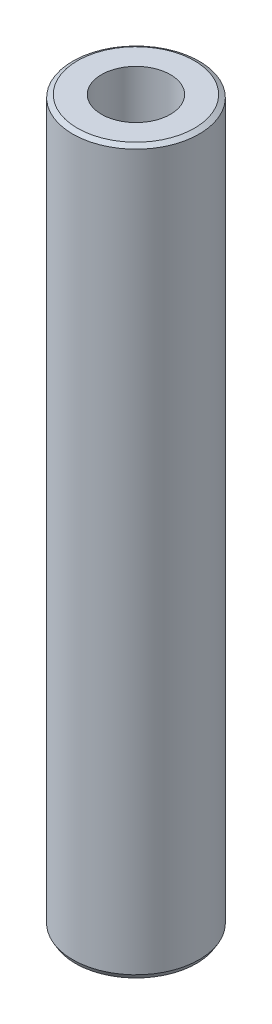
SolidWorks part; units mm, degrees
ref_plane "Front Plane" through (0, 0, 0) normal (0, 0, 1) x (1, 0, 0)
ref_plane "Top Plane" through (0, 0, 0) normal (0, 1, 0) x (1, 0, 0)
ref_plane "Right Plane" through (0, 0, 0) normal (1, 0, 0) x (0, 0, -1)
sketch "Sketch1" plane through (0, 0, 0) normal (0, 1, 0) x (1, 0, 0)
  circle A0 centre (0, 0) radius 52.5
  dimension "SHAFT_OD" = 105
extrude "Boss-Extrude1" add sketch "Sketch1" along normal blind 600
sketch "Sketch2" plane through (0, 0, 0) normal (0, 1, 0) x (1, 0, 0)
  circle A0 centre (0, 0) radius 28.6177
  dimension "BORE_D" = 57.2355
extrude "Cut-Extrude1" cut sketch "Sketch2" along normal through all
chamfer "Chamfer1" distance 2.2574 angle 60 2 edges at (0, 600, 52.5) (0, 0, 52.5) first distance on face at (0, 600, 52.5) first distance on face at (0, 0, 28.6177)
